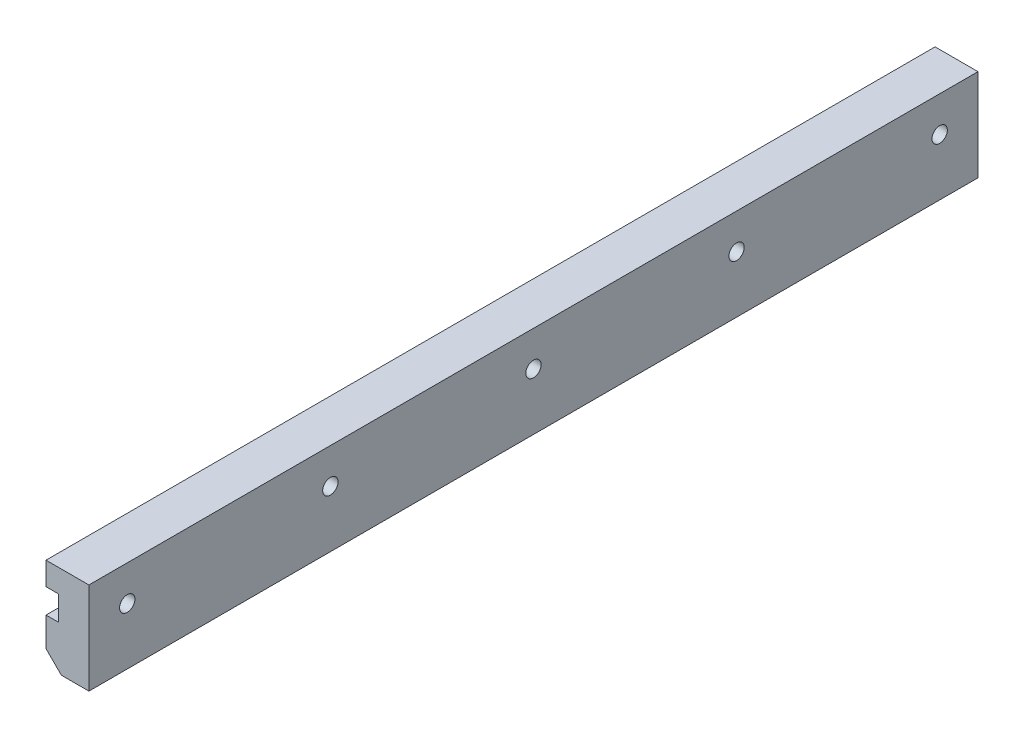
SolidWorks part; units mm, degrees
ref_plane "Front Plane" through (0, 0, 0) normal (0, 0, 1) x (1, 0, 0)
ref_plane "Top Plane" through (0, 0, 0) normal (0, 1, 0) x (1, 0, 0)
ref_plane "Right Plane" through (0, 0, 0) normal (1, 0, 0) x (0, 0, -1)
sketch "Sketch1" plane through (0, 0, 0) normal (0, 0, 1) x (1, 0, 0)
  line L0 (0, 0) -> (0, 60)
  line L1 (0, 0) -> (-18, 0)
  line L2 (-28, 45) -> (-28, 60)
  line L3 (-28, 10) -> (-18, 0)
  line L4 (-28, 60) -> (0, 60)
  line L5 (-28, 60) -> (-28, 45)
  line L6 (-28, 45) -> (-20, 45)
  line L7 (-20, 45) -> (-20, 29)
  line L8 (-20, 29) -> (-28, 29)
  line L9 (-28, 29) -> (-28, 10)
  dimension "D1" = 60
  dimension "D2" = 28
  dimension "D3" = 15
  dimension "D4" = 8
  dimension "D5" = 16
extrude "Boss-Extrude1" add sketch "Sketch1" against normal blind 580 contours L8 L9 L3 L1 L0 L4 L2 L6 L7 region at (-12.7927, 30.2912, 0)
sketch "Sketch2" plane through (0, 0, 0) normal (1, 0, 0) x (0, 0, -1)
  line L0 (25, 37) -> (157.5, 37) construction
  circle A0 centre (25, 37) radius 5
  circle A1 centre (157.5, 37) radius 5
  circle A2 centre (290, 37) radius 5
  circle A3 centre (422.5, 37) radius 5
  circle A4 centre (555, 37) radius 5
  dimension "D3" = 10
  dimension "D1" = 132.5
  dimension "D2" = 5
extrude "Cut-Extrude1" cut sketch "Sketch2" against normal through all
